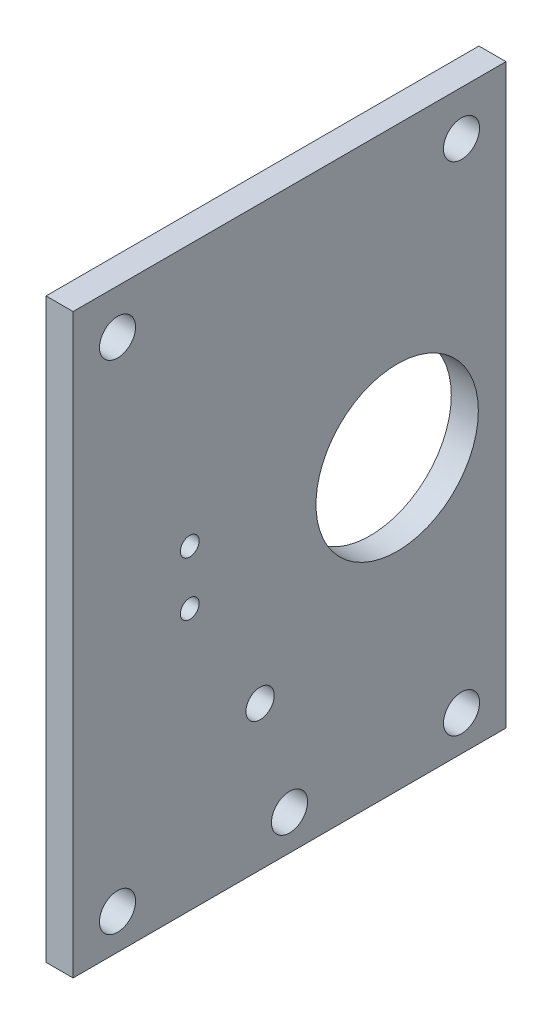
SolidWorks part; units mm, degrees
material "6061 Alloy"
ref_plane "Front Plane" through (0, 0, 0) normal (0, 0, 1) x (1, 0, 0)
ref_plane "Top Plane" through (0, 0, 0) normal (0, 1, 0) x (1, 0, 0)
ref_plane "Right Plane" through (0, 0, 0) normal (1, 0, 0) x (0, 0, -1)
sketch "Sketch2" plane through (0, 0, 0) normal (1, 0, 0) x (0, 0, -1)
  line L1 (-38.1, -50.8) -> (38.1, -50.8)
  line L2 (-38.1, -50.8) -> (-38.1, 50.8)
  line L3 (-38.1, 50.8) -> (38.1, 50.8)
  line L4 (38.1, -50.8) -> (38.1, 50.8)
  line L5 (-38.1, -50.8) -> (38.1, 50.8) construction
  line L6 (-38.1, 50.8) -> (38.1, -50.8) construction
  point P0 (0, 0)
  dimension "D1" = 76.2
  dimension "D2" = 101.6
extrude "Boss-Extrude1" add sketch "Sketch2" along normal blind 4.7625
sketch "Sketch3" plane through (4.7625, 0, 0) normal (1, 0, 0) x (0, 0, -1)
  line L5 (30.2768, -44.5643) -> (-30.2768, -44.5643) construction
  line L6 (-30.2768, 42.9768) -> (30.2768, 42.9768) construction
  line L7 (30.2768, 42.9768) -> (30.2768, -44.5643) construction
  line L8 (-30.2768, 42.9768) -> (-30.2768, -44.5643) construction
  line L9 (-38.1, 50.8) -> (-38.1, -50.8) construction
  line L10 (38.1, 50.8) -> (-38.1, 50.8) construction
  line L11 (38.1, -50.8) -> (38.1, 50.8) construction
  line L12 (-38.1, -50.8) -> (38.1, -50.8) construction
  circle A0 centre (30.2768, -44.5643) radius 3.175
  circle A1 centre (30.2768, 42.9768) radius 3.175
  circle A2 centre (-30.2768, 42.9768) radius 3.175
  circle A3 centre (-30.2768, -44.5643) radius 3.175
  circle A4 centre (18.9484, 0) radius 14.2875
  circle A5 centre (-5.1816, -25.4) radius 2.4892
  circle A6 centre (0, -44.5643) radius 3.175
  dimension "D1" = 6.35
  dimension "D5" = 7.8232
  dimension "D7" = 7.8232
  dimension "D8" = 6.2357
  dimension "D9" = 28.575
  dimension "D10" = 50.8
  dimension "D11" = 4.9784
  dimension "D12" = 25.4
  dimension "D6" = 7.8232
  dimension "D13" = 24.13
  dimension "D14" = 19.1516
extrude "Cut-Extrude1" cut sketch "Sketch3" against normal blind 6.35 contours A1
extrude "Cut-Extrude2" cut sketch "Sketch3<4>" against normal blind 6.35
sketch "Sketch3<4>" plane through (4.7625, 0, 0) normal (1, 0, 0) x (0, 0, -1) same geometry as "Sketch3"
hole_wizard "M6 Clearance Hole1" positions "Sketch5" profile "Sketch4" hole size "M4x0.7" standard "ANSI Metric" end condition up to next
sketch "Sketch5" plane through (4.7625, 0, 0) normal (1, 0, 0) x (0, 0, -1)
  circle A0 centre (-17.5641, -4.7625) radius 1.65 construction
  circle A1 centre (-17.5641, 4.7625) radius 1.65 construction
  point P0 (-17.5641, 4.7625)
  point P2 (-17.5641, -4.7625)
sketch "Sketch4" plane through (4.7625, 4.7625, 17.5641) normal (0, 1, 0) x (0, 0, -1)
  line L0 (0, 0) -> (0, 4.7625)
  line L1 (0, 4.7625) -> (1.65, 4.7625)
  line L2 (1.65, 4.7625) -> (1.65, 0)
  line L5 (1.65, 0) -> (0, 0)
  line L11 (0, -6.35) -> (0, 107.95) construction
  dimension "Thru Hole Dia." = 3.3
  dimension "Thru Hole Depth" = 4.7625
